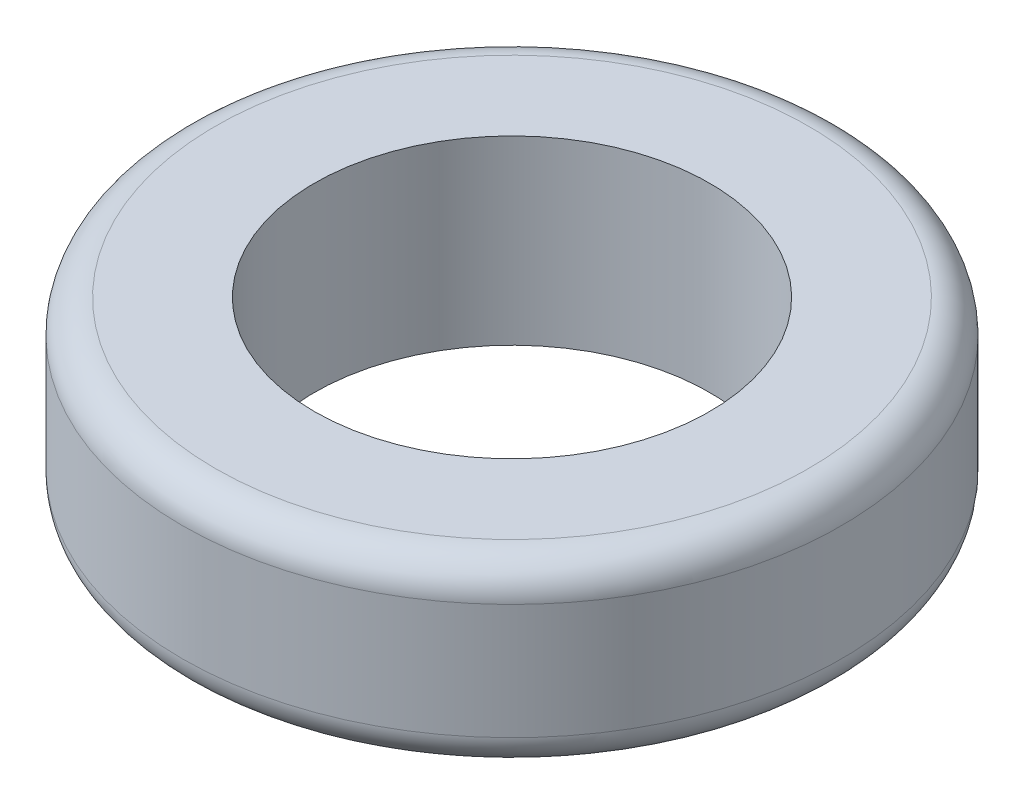
SolidWorks part; units mm, degrees
ref_plane "Front Plane" through (0, 0, 0) normal (0, 0, 1) x (1, 0, 0)
ref_plane "Top Plane" through (0, 0, 0) normal (0, 1, 0) x (1, 0, 0)
ref_plane "Right Plane" through (0, 0, 0) normal (1, 0, 0) x (0, 0, -1)
ref_axis "X-Axis" through (88.99, 0, 0) along (-1, 0, 0)
ref_axis "Y-Axis" through (0, 0, -88.99) along (0, 0, 1)
ref_axis "Z-Axis" through (0, -55, 0) along (0, 1, 0)
sketch "Sketch1" plane through (0, 0, 0) normal (0, 1, 0) x (1, 0, 0)
  circle A0 centre (0, 0) radius 10
  circle A1 centre (0, 0) radius 6
  dimension "D1" = 12
  dimension "D2" = 4
extrude "Boss-Extrude1" add sketch "Sketch1" along normal blind 5.5
fillet "Fillet1" radius 1 2 edges at (0, 0, 10) (0, 5.5, 10)
